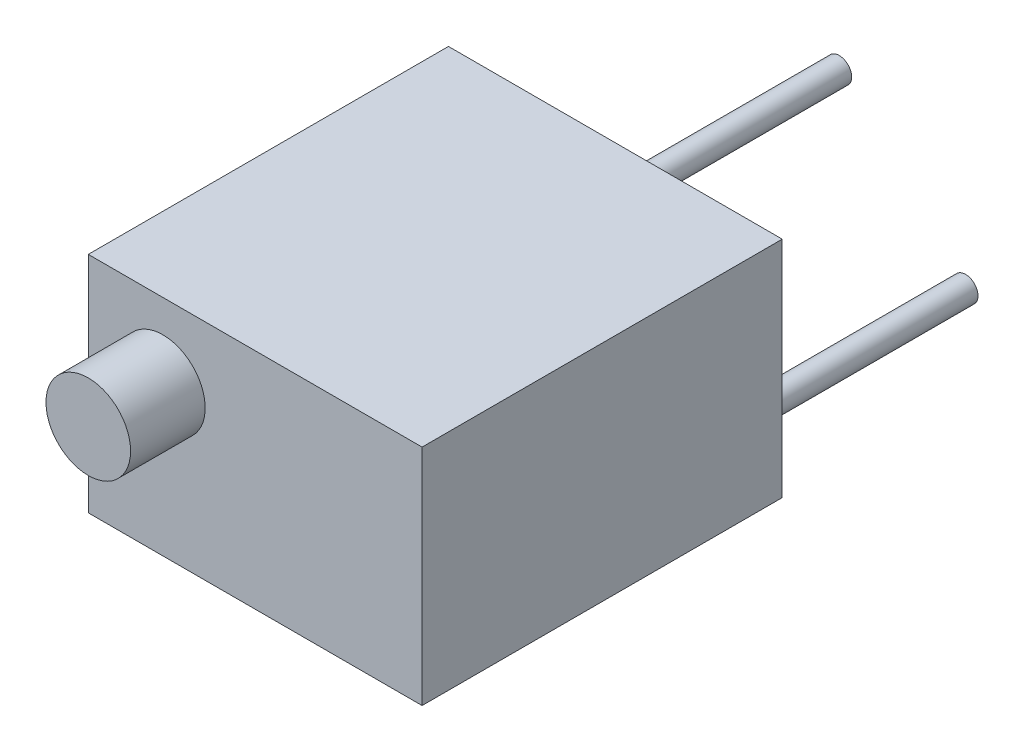
SolidWorks part; units mm, degrees
ref_plane "前视" through (0, 0, 0) normal (0, 0, 1) x (1, 0, 0)
ref_plane "上视" through (0, 0, 0) normal (0, 1, 0) x (1, 0, 0)
ref_plane "右视" through (0, 0, 0) normal (1, 0, 0) x (0, 0, -1)
sketch "草图1" plane through (0, 0, 0) normal (0, 1, 0) x (1, 0, 0)
  line L0 (0, 81.3418) -> (0, -101.3275) construction
  line L1 (-87.3375, 0) -> (113.7186, 0) construction
  line L3 (-3.355, 3.62) -> (3.355, 3.62)
  line L4 (-3.355, 3.62) -> (-3.355, -3.62)
  line L5 (-3.355, -3.62) -> (3.355, -3.62)
  line L6 (3.355, 3.62) -> (3.355, -3.62)
  dimension "D1" = 6.71
  dimension "D2" = 7.24
extrude "拉伸1" add sketch "草图1" along normal blind 2.25 and the other way blind 2.25
sketch "草图3" plane through (0, 0, -3.62) normal (0, 0, -1) x (-1, 0, 0)
  line L0 (-3.4455, -1.27) -> (3.0961, -1.27) construction
  line L1 (-1.9445, 0) -> (1.7241, 0) construction
  line L2 (0, 5.9307) -> (0, -2.165) construction
  line L3 (-1.9445, 1.27) -> (1.7241, 1.27) construction
  circle A0 centre (0, 1.27) radius 0.25
  circle A1 centre (2.54, -1.27) radius 0.25
  circle A2 centre (-2.54, -1.27) radius 0.25
  dimension "D1" = 0.5
  dimension "D5" = 0.5
  dimension "D2" = 5.08
  dimension "D3" = 2.54
  dimension "D4" = 1.27
extrude "拉伸3" add sketch "草图3" along normal blind 4.5
sketch "草图4" plane through (0, 0, 3.62) normal (0, 0, 1) x (1, 0, 0)
  line L0 (-3.355, 2.25) -> (-3.355, -2.25) construction
  line L1 (-3.355, 2.25) -> (3.355, 2.25) construction
  circle A0 centre (-1.855, 0.75) radius 0.85
  dimension "D1" = 1.7
  dimension "D2" = 1.5
  dimension "D3" = 1.5
extrude "拉伸4" add sketch "草图4" along normal blind 1.5
